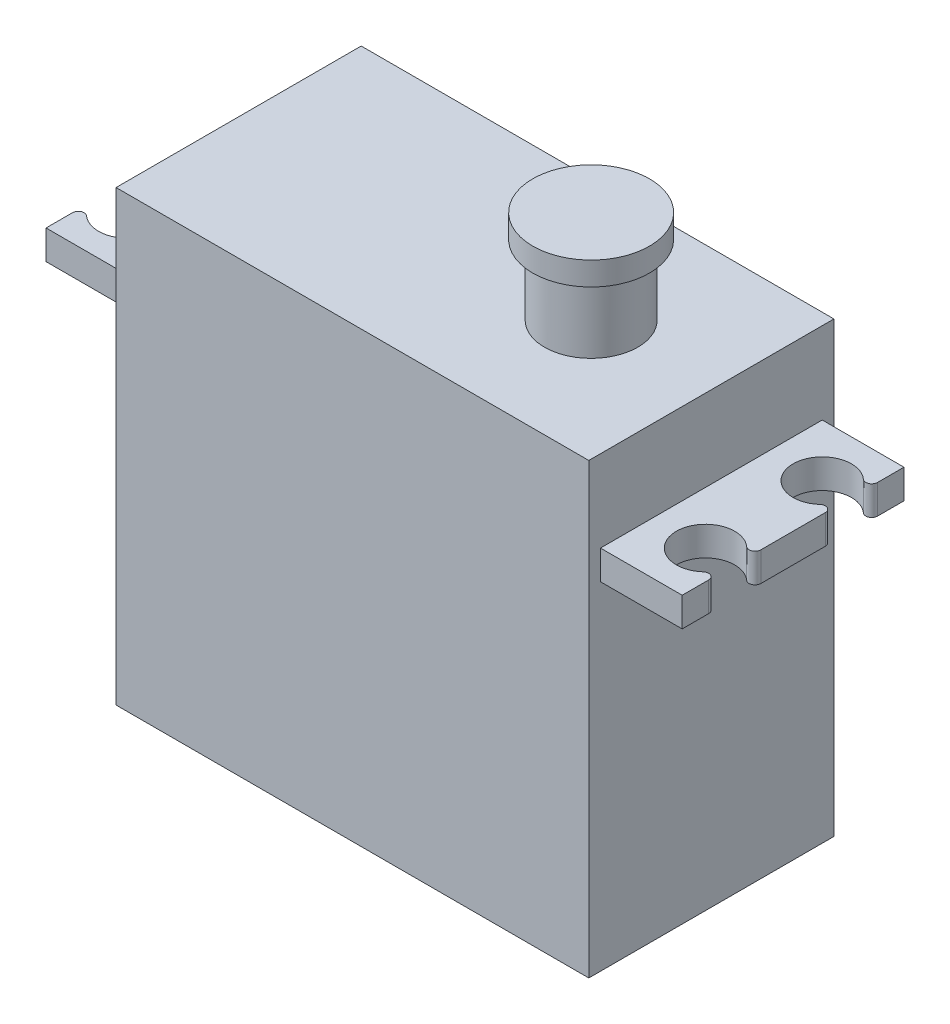
SolidWorks part; units mm, degrees
material "AISI 1015 Steel, Cold Drawn (SS)"
ref_plane "Front Plane" through (0, 0, 0) normal (0, 0, 1) x (1, 0, 0)
ref_plane "Top Plane" through (0, 0, 0) normal (0, 1, 0) x (1, 0, 0)
ref_plane "Right Plane" through (0, 0, 0) normal (1, 0, 0) x (0, 0, -1)
sketch "Sketch1" plane through (0, 0, 0) normal (0, 1, 0) x (1, 0, 0)
  line L0 (0, 98.4413) -> (0, -50.6259) construction
  line L1 (-20.25, -10.5) -> (20.25, -10.5)
  line L2 (-20.25, -10.5) -> (-20.25, 10.5)
  line L3 (-20.25, 10.5) -> (20.25, 10.5)
  line L4 (20.25, -10.5) -> (20.25, 10.5)
  line L5 (-20.25, -10.5) -> (20.25, 10.5) construction
  line L6 (-20.25, 10.5) -> (20.25, -10.5) construction
  line L7 (-67.6585, 0) -> (91.571, 0) construction
  point P0 (0, 0)
  dimension "D1" = 40.5
  dimension "D2" = 21
extrude "Boss-Extrude1" add sketch "Sketch1" along normal blind 38.4
sketch "Sketch2" plane through (0, 38.4, 0) normal (0, 1, 0) x (1, 0, 0)
  line L0 (-25.3405, 0) -> (25.583, 0) construction
  line L1 (20.25, -10.5) -> (20.25, 10.5) construction
  circle A0 centre (9.95, 0) radius 4
  dimension "D2" = 8
  dimension "D1" = 10.3
extrude "Boss-Extrude2" add sketch "Sketch2" along normal blind 6
sketch "Sketch3" plane through (0, 44.4, 0) normal (0, 1, 0) x (1, 0, 0)
  circle A0 centre (9.95, 0) radius 4
  circle A1 centre (9.95, 0) radius 5
  circle M1 centre (9.95, 0) radius 4
  dimension "D1" = 10
extrude "Boss-Extrude3" add sketch "Sketch3" along normal blind 2 separate body contours M1 | A1 M1 region at (9.95, 44.4, 0) region at (5.0914, 44.4, 0)
sketch "Sketch6" plane through (0, 44.4, 0) normal (0, -1, 0) x (1, 0, 0)
  line L0 (0, 10.5) -> (0, -10.5) construction
  line L1 (27.25, 0) -> (-27.25, 0) construction
  line L2 (9.95, 9.5) -> (9.95, -9.5) construction
  line L3 (20.25, 10.5) -> (20.25, -10.5) construction
  line L4 (-27.25, -7.2361) -> (-27.25, -9.5)
  line L5 (27.25, 9.5) -> (-27.25, 9.5)
  line L6 (27.25, 9.5) -> (27.25, 7.2361)
  line L7 (27.25, -9.5) -> (-27.25, -9.5)
  line L8 (-27.25, 9.5) -> (-27.25, 7.2361)
  line L9 (27.25, 9.5) -> (-27.25, -9.5) construction
  line L10 (27.25, -9.5) -> (-27.25, 9.5) construction
  line L11 (-27.25, 2.7639) -> (-27.25, -2.7639)
  line L12 (27.25, 2.7639) -> (27.25, -2.7639)
  line L13 (-20.25, 10.5) -> (20.25, 10.5) construction
  line L14 (20.25, -10.5) -> (-20.25, -10.5) construction
  line L17 (27.25, -7.2361) -> (27.25, -9.5)
  arc A0 (26.4167, 6.8634) -> (26.4167, 3.1366) centre (24.75, 5) ccw
  arc A1 (26.4167, 6.8634) -> (27.25, 7.2361) centre (26.75, 7.2361) ccw
  arc A2 (27.25, 2.7639) -> (26.4167, 3.1366) centre (26.75, 2.7639) ccw
  arc A3 (27.25, -2.7639) -> (26.4167, -3.1366) centre (26.75, -2.7639) cw
  arc A4 (26.4167, -6.8634) -> (27.25, -7.2361) centre (26.75, -7.2361) cw
  arc A5 (26.4167, -6.8634) -> (26.4167, -3.1366) centre (24.75, -5) cw
  arc A6 (-27.25, 2.7639) -> (-26.4167, 3.1366) centre (-26.75, 2.7639) cw
  arc A7 (-26.4167, 6.8634) -> (-27.25, 7.2361) centre (-26.75, 7.2361) cw
  arc A8 (-26.4167, 6.8634) -> (-26.4167, 3.1366) centre (-24.75, 5) cw
  arc A9 (-26.4167, -6.8634) -> (-26.4167, -3.1366) centre (-24.75, -5) ccw
  arc A10 (-26.4167, -6.8634) -> (-27.25, -7.2361) centre (-26.75, -7.2361) ccw
  arc A11 (-27.25, -2.7639) -> (-26.4167, -3.1366) centre (-26.75, -2.7639) ccw
  point P9 (0, 0)
  dimension "D3" = 5
  dimension "D7" = 0.5
  dimension "D1" = 10.3
  dimension "D2" = 19
  dimension "D4" = 14.8
  dimension "D5" = 5
  dimension "D6" = 54.5
extrude "Boss-Extrude5" add sketch "Sketch6" against normal blind 2.5 from offset 15.5
